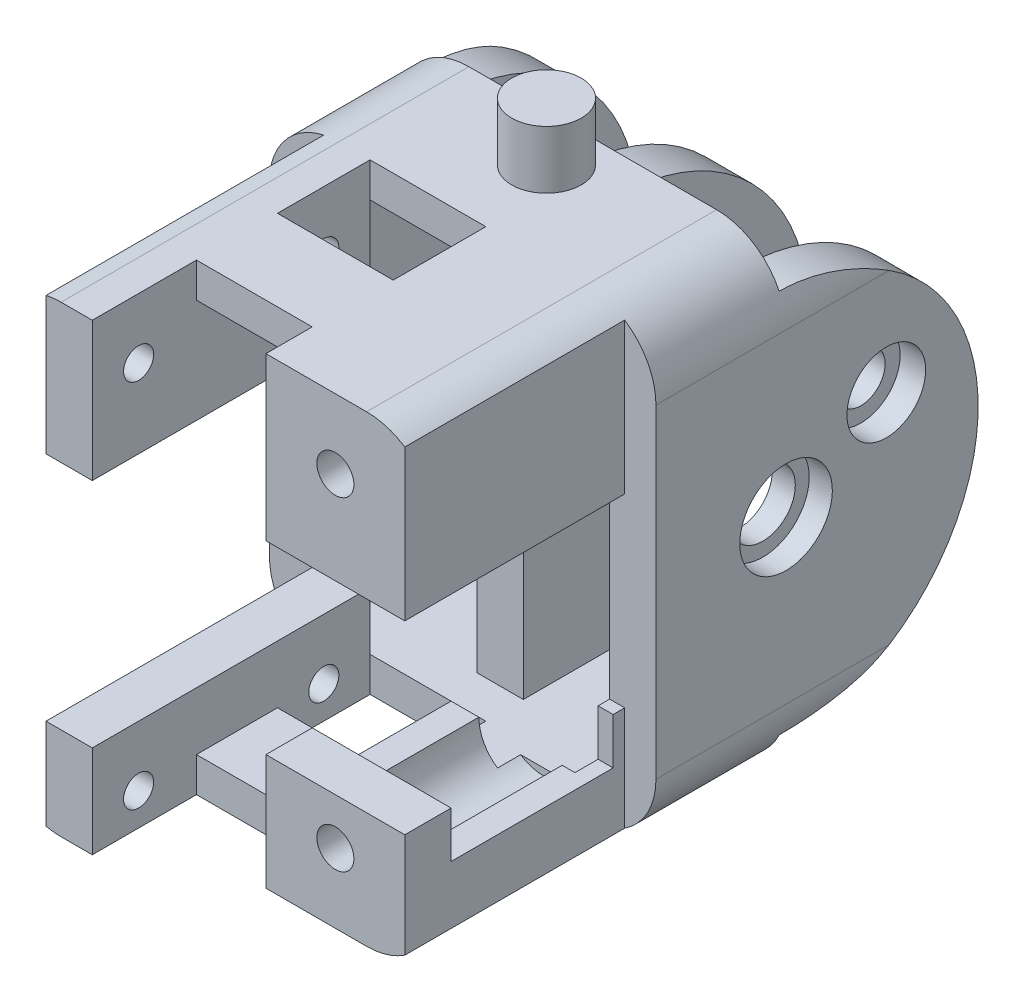
SolidWorks part; units mm, degrees
ref_plane "Front" through (0, 0, 0) normal (0, 0, 1) x (1, 0, 0)
ref_plane "Top" through (0, 0, 0) normal (0, 1, 0) x (1, 0, 0)
ref_plane "Right" through (0, 0, 0) normal (1, 0, 0) x (0, 0, -1)
sketch "Sketch1" plane through (0, 0, 0) normal (0, 0, 1) x (1, 0, 0)
  line L0 (8.35, -7) -> (8.35, 7)
  line L1 (-5.95, -8.5) -> (5.95, -8.5)
  line L2 (-6.35, -8.1) -> (-6.35, 8.1)
  line L3 (-5.95, 8.5) -> (5.95, 8.5)
  line L4 (6.35, -8.1) -> (6.35, 8.1)
  line L7 (-5.35, 10) -> (5.35, 10)
  line L8 (-8.35, -7) -> (-8.35, 7)
  line L9 (-5.35, -10) -> (5.35, -10)
  arc A8 (-5.95, 8.5) -> (-6.35, 8.1) centre (-5.95, 8.1) ccw
  arc A9 (6.35, 8.1) -> (5.95, 8.5) centre (5.95, 8.1) ccw
  arc A10 (5.95, -8.5) -> (6.35, -8.1) centre (5.95, -8.1) ccw
  arc A11 (-6.35, -8.1) -> (-5.95, -8.5) centre (-5.95, -8.1) ccw
  arc A13 (8.35, 7) -> (5.35, 10) centre (5.35, 7) ccw
  arc A14 (5.35, -10) -> (8.35, -7) centre (5.35, -7) ccw
  arc A15 (-8.35, -7) -> (-5.35, -10) centre (-5.35, -7) ccw
  arc A16 (-5.35, 10) -> (-8.35, 7) centre (-5.35, 7) ccw
  point P0 (0, 0)
  dimension "D1" = 3
  dimension "D6" = 3
  dimension "D9" = 3
  dimension "D2" = 0.4
  dimension "D3" = 0.4
  dimension "D5" = 0.4
  dimension "D7" = 0.4
  dimension "D8" = 3
  dimension "D4" = 16.7
extrude "Boss-Extrude1" add sketch "Sketch1" along normal blind 18 and the other way blind 12
sketch "Sketch9" plane through (0, 10, 0) normal (0, 1, 0) x (1, 0, 0)
  circle A0 centre (0, 0) radius 1.5
  dimension "D1" = 3
extrude "Boss-Extrude4" add sketch "Sketch9" along normal blind 2.5
sketch "Sketch10" plane through (0, -10, 0) normal (0, -1, 0) x (1, 0, 0)
  circle A0 centre (0, 0) radius 1.5
  dimension "D1" = 3
extrude "Boss-Extrude5" add sketch "Sketch10" along normal blind 2.5 contours A0
ref_plane "Plane1" through (0, 0, 3.5) normal (0, 0, 1) x (1, 0, 0)
sketch "Sketch16" plane through (0, 0, 3.5) normal (0, 0, 1) x (1, 0, 0)
  line L0 (8.35, -5.5) -> (8.35, 5.5)
  line L1 (-3.1, -8.5) -> (3.1, -8.5)
  line L2 (-6.1, -5.5) -> (-6.1, 5.5)
  line L3 (-3.1, 8.5) -> (4.3, 8.5)
  line L4 (6.1, -5.5) -> (6.1, 6.7)
  line L5 (-6.1, -8.5) -> (6.1, 8.5) construction
  line L6 (-6.1, 8.5) -> (6.1, -8.5) construction
  line L7 (-3.85, 10) -> (3.85, 10)
  line L8 (-8.35, -5.5) -> (-8.35, 5.5)
  line L9 (-3.85, -10) -> (3.85, -10)
  line L10 (0, 0) -> (0, -7)
  line L11 (0, -8.5) -> (0, -5.5)
  line L12 (0, -11.4125) -> (0, 11.4125) construction
  line L13 (0, -6) -> (-5, -6)
  line L14 (5, 0) -> (5, 6)
  line L15 (0, 0) -> (12.2753, 0) construction
  line L16 (0, 6) -> (5, 6)
  line L17 (0, 6) -> (-5, 6)
  line L18 (0, -6) -> (5, -6)
  line L19 (5, 0) -> (5, -6)
  line L20 (-5, 0) -> (-5, -6)
  line L21 (-5, 0) -> (-5, 6)
  line L22 (-6.058, 6) -> (-6.1, 6)
  arc A0 (3.1, -8.5) -> (6.1, -5.5) centre (3.1, -5.5) ccw
  arc A1 (-3.1, -8.5) -> (-6.1, -5.5) centre (-3.1, -5.5) cw
  arc A2 (4.3, 8.5) -> (6.1, 6.7) centre (4.3, 6.7) cw
  arc A3 (-6.1, 5.5) -> (-3.1, 8.5) centre (-3.1, 5.5) cw
  arc A4 (3.85, 10) -> (8.35, 5.5) centre (3.85, 5.5) cw
  arc A5 (-8.35, 5.5) -> (-3.85, 10) centre (-3.85, 5.5) cw
  arc A6 (-3.85, -10) -> (-8.35, -5.5) centre (-3.85, -5.5) cw
  arc A7 (3.85, -10) -> (8.35, -5.5) centre (3.85, -5.5) ccw
  circle A9 centre (0, 7) radius 0.6
  circle A11 centre (0, -7) radius 0.6
  circle A12 centre (0, 0) radius 5
  point P0 (-1.1, 0)
  dimension "D1" = 3
  dimension "D8" = 4.5
  dimension "D9" = 1.8
  dimension "D10" = 4.5
  dimension "D2" = 17
  dimension "D3" = 16.7
  dimension "D4" = 2.25
  dimension "D5" = 2.25
  dimension "D6" = 1.5
  dimension "D7" = 1.5
sketch "Sketch21" plane through (0, 0, 0) normal (1, 0, 0) x (0, 0, -1)
  line L0 (0, 0) -> (2, 0) construction
  line L1 (2, 0) -> (6.3301, 2.5) construction
  circle A0 centre (2, 0) radius 1.4
  circle A1 centre (6.3301, 2.5) radius 1.05
  circle A2 centre (2, 0) radius 5 construction
extrude "Extrude7" cut sketch "Sketch21" against normal through all both and the other way through all contours A0 L0 L1 | L0 A0 L1 region at (0, 0, -2)
sketch "Sketch23" plane through (0, 0, 0) normal (1, 0, 0) x (0, 0, -1)
  line L0 (2, 9.5) -> (2, 10)
  line L2 (2, -8.3) -> (2, -11.4416)
  line L4 (-9.4737, 11.5383) -> (19.1929, 11.5383)
  line L5 (-9.4737, 11.5383) -> (-9.4737, -11.4416)
  line L6 (2, 13.0446) -> (2, 10)
  line L7 (2, 4) -> (2, 9.5)
  line L8 (-9.4737, -11.4416) -> (19.1929, -11.4416)
  line L9 (2, -10.6179) -> (2, -4)
  line L10 (19.1929, 11.5383) -> (19.1929, -11.4416)
  circle A2 centre (2, 0) radius 4
  circle A4 centre (2, 0) radius 8.3
extrude "Extrude8" cut sketch "Sketch23" against normal through all both and the other way through all contours L2 L6 L0 region at (0, 0.0666, -12.5103)
sketch "Sketch25" plane through (0, 0, 0) normal (1, 0, 0) x (0, 0, -1)
  circle A0 centre (2, 0) radius 2
extrude "Extrude9" cut sketch "Sketch25" along normal blind 10 from offset 7.35 contours A0 region at (0, 0, -2)
mirror "Mirror1" about plane through (0, 0, 0) normal (1, 0, 0) of "Extrude9"
sketch "Sketch26" plane through (-7.35, 0, 0) normal (-1, 0, 0) x (0, 0, 1)
  line L13 (-2, 2.3671) -> (-4.05, 1.1836)
  line L14 (-4.05, 1.1836) -> (-4.05, -1.1836)
  line L15 (-4.05, -1.1836) -> (-2, -2.3671)
  line L16 (-2, -2.3671) -> (0.05, -1.1836)
  line L17 (0.05, -1.1836) -> (0.05, 1.1836)
  line L18 (0.05, 1.1836) -> (-2, 2.3671)
  circle A0 centre (-2, 0) radius 2.05 construction
extrude "Extrude10" cut sketch "Sketch26" along normal blind 10
sketch "Sketch27" plane through (0, 0, 0) normal (0, 1, 0) x (1, 0, 0)
  line L2 (-6.35, 10.3) -> (-6.35, 2.8)
  line L3 (0, 0) -> (0, 7.98)
  line L4 (6.35, 10.3) -> (6.35, 2.8)
  line L6 (-6.35, 10.3) -> (6.35, 10.3)
  line L7 (-5.55, 2) -> (0, 2)
  line L9 (0, 2) -> (5.55, 2)
  arc A6 (1.9843, 2.25) -> (-1.9843, 2.25) centre (0, 0) ccw
  arc A7 (-1.9843, 2.25) -> (-2.6458, 2) centre (-2.6458, 3) cw
  arc A8 (2.6458, 2) -> (1.9843, 2.25) centre (2.6458, 3) cw
  arc A9 (6.35, 2.8) -> (5.55, 2) centre (5.55, 2.8) cw
  arc A10 (-6.35, 2.8) -> (-5.55, 2) centre (-5.55, 2.8) ccw
  circle A11 centre (0, 0) radius 3
  dimension "D1" = 1
  dimension "D2" = 1
  dimension "D3" = 0.8
  dimension "D4" = 0.8
sketch "Sketch29" plane through (0, 0, 0) normal (0, 1, 0) x (1, 0, 0)
  circle A0 centre (0, 0) radius 3.5
extrude "Extrude12" add sketch "Sketch29" along normal blind 1.5 from offset 8.5
mirror "Mirror2" about plane through (0, 0, 0) normal (0, 1, 0) of "Extrude12"
extrude "Extrude13" cut sketch "Sketch27" against normal through all both and the other way through all contours L2 A10 L7 A7 A6 A8 L9 A9 L4 L6 | L9 A11 A6 L3 | A6 A11 L7 L3 | A11 A7 L7 | A11 L9 A8 region at (0, 0, -10.1483) region at (-2.2729, 0, -2.0529) region at (-0.8609, 0, -2.4063) region at (2.2729, 0, -2.0529) region at (0.8609, 0, -2.4063)
sketch "Sketch30" plane through (0, 0, 0) normal (1, 0, 0) x (0, 0, -1)
  line L0 (7, 0) -> (16.1032, 0) construction
  line L1 (0, 10) -> (-1.5, 10)
  line L2 (0, -8.5) -> (0, -14.6222)
  line L3 (-2, -10) -> (2, -10)
  line L5 (2, 8.3) -> (2, 10)
  line L6 (2, 10) -> (-1.5, 10)
  line L7 (2, -8.3) -> (2, -10)
  line L9 (0, 0) -> (-14, 0)
  line L11 (-2, -10) -> (0, -10)
  line L12 (0, 50) -> (0, -50) construction
  line L13 (-1.5, 10) -> (0, 10)
  line L14 (3, 8.5) -> (-9.1346, 8.5) construction
  line L15 (3, -8.5) -> (-1.0266, -8.5) construction
  line L16 (2, 0) -> (7, 0)
  line L18 (0, 0) -> (-2, 0)
  line L21 (-14, -10) -> (-14, 10)
  line L22 (2, 10) -> (-18, 10) construction
  line L23 (-14, 10) -> (-1.5, 10)
  line L24 (-14, -10) -> (-1.5, -10)
  line L25 (-2, 0) -> (-2, 13.6859)
  line L26 (-2, 0) -> (-2, -12.5408)
  arc A12 (2, -8.3) -> (2, 8.3) centre (2, 0) ccw
extrude "Extrude14" add sketch "Sketch30" along normal blind 1 and the other way blind 1 contours L11 | L3 | L13 | L1 | L11 | A12 | A12 region at (0, 9.7652, -1)
extrude "Extrude15" cut sketch "Sketch" along normal blind 10 and the other way blind 2 contours A1 region at (0, 2.5, -6.3301)
sketch "Sketch" plane through (0, 0, 0) normal (1, 0, 0) x (0, 0, -1) same geometry as "Sketch21"
sketch "Sketch32" plane through (0, 0, 0) normal (1, 0, 0) x (0, 0, -1)
  circle A0 centre (6.3301, 2.5) radius 1.7
extrude "Extrude17" cut sketch "Sketch32" along normal through all from offset 7.25
sketch "Sketch37" plane through (0, 0, 0) normal (1, 0, 0) x (0, 0, -1)
  circle A0 centre (2, 0) radius 1.35
extrude "Extrude22" cut sketch "Sketch37" against normal through all both and the other way through all
sketch "Sketch54" plane through (-1, 0, 0) normal (-1, 0, 0) x (0, 0, 1)
  line L1 (-5.5604, 4.3058) -> (-7.5091, 4.0695)
  line L2 (-7.5091, 4.0695) -> (-8.2788, 2.2637)
  line L3 (-8.2788, 2.2637) -> (-7.0999, 0.6942)
  line L4 (-7.0999, 0.6942) -> (-5.1512, 0.9305)
  line L5 (-5.1512, 0.9305) -> (-4.3814, 2.7363)
  line L6 (-4.3814, 2.7363) -> (-5.5604, 4.3058)
  circle A0 centre (-6.3301, 2.5) radius 1.7 construction
extrude "Extrude33" cut sketch "Sketch54" against normal blind 1.5
sketch "Sketch58" plane through (0, 0, 0) normal (1, 0, 0) x (0, 0, -1)
  line L0 (2, 0) -> (2, 17.3029) construction
  line L4 (-13.12, 0.097) -> (-13.12, -6.903)
  line L5 (-13.12, -6.903) -> (-5.58, -6.903)
  line L6 (-5.58, -6.903) -> (-5.58, 7.097)
  line L7 (-5.58, 7.097) -> (-13.12, 7.097)
  line L8 (-13.12, 7.097) -> (-13.12, 0.097)
  line L9 (-13.12, -6.903) -> (-13.12, -15.8392)
  line L10 (-13.12, -15.8392) -> (-23.547, -15.8392)
  line L11 (-23.547, -15.8392) -> (-23.547, 13.1188)
  line L12 (-23.547, 13.1188) -> (-13.12, 13.1188)
  line L13 (-13.12, 13.1188) -> (-13.12, 7.097)
  dimension "D1" = 15.12
extrude "Extrude36" cut sketch "Sketch58" along normal through all contours L13 L12 L11 L10 L9 L4 L8 region at (0, -1.3602, 18.3335)
sketch "Sketch60" plane through (0, 0, 13.12) normal (0, 0, 1) x (1, 0, 0)
  line L0 (0, 0) -> (4, 0)
  line L1 (50, 0) -> (-50, 0) construction
  line L2 (4, 0) -> (4, 7)
  line L3 (4, 0) -> (4, -7)
  line L5 (7, 3) -> (1, 3)
  line L6 (7, 3) -> (7, 11)
  line L7 (7, 11) -> (1, 11)
  line L8 (1, 3) -> (1, 11)
  line L9 (7, 3) -> (1, 11) construction
  line L10 (7, 11) -> (1, 3) construction
  line L15 (7, -9) -> (1, -9)
  line L16 (7, -9) -> (7, -5)
  line L17 (7, -5) -> (1, -5)
  line L18 (1, -9) -> (1, -5)
  line L19 (7, -9) -> (1, -5) construction
  line L20 (7, -5) -> (1, -9) construction
  circle A0 centre (4, 7) radius 0.8
  circle A1 centre (4, -7) radius 0.8
  arc M18 (6.35, -8.1) -> (5.95, -8.5) centre (5.95, -8.1) cw
  line M19 (5.95, -8.5) -> (0, -8.5)
  line M23 (0, 8.5) -> (5.95, 8.5)
  arc M24 (5.95, 8.5) -> (6.35, 8.1) centre (5.95, 8.1) cw
  line M25 (6.35, 8.1) -> (6.35, -8.1)
  dimension "D1" = 4
  dimension "D2" = 7
  dimension "D3" = 7
extrude "Extrude37" add sketch "Sketch60" against normal blind 8 contours A0 L5 L8 M25 M24 M23 | A1 L17 L18 M19 M18 M25 region at (3.6479, 5.6549, 13.12) region at (5.175, -5.0639, 13.12)
sketch "Sketch61" plane through (0, 0, 13.12) normal (0, 0, 1) x (1, 0, 0)
  line L0 (7, 11) -> (7, 12.9518)
  line L1 (7, 3) -> (1, 3)
  line L2 (7, 3) -> (7, 11)
  line L3 (7, 11) -> (1, 11)
  line L4 (1, 3) -> (1, 11)
  line L5 (7, 3) -> (1, 11) construction
  line L6 (7, 11) -> (1, 3) construction
  line L7 (7, -9) -> (1, -9)
  line L8 (7, -9) -> (7, -5)
  line L9 (7, -5) -> (1, -5)
  line L10 (1, -9) -> (1, -5)
  line L11 (7, -9) -> (1, -5) construction
  line L12 (7, -5) -> (1, -9) construction
  line L13 (7, 12.9518) -> (12.7978, 12.9518)
  line L14 (12.7978, 12.9518) -> (12.7978, -12.6418)
  line L15 (12.7978, -12.6418) -> (7, -12.6418)
  line L16 (7, -12.6418) -> (7, -9)
  line L17 (1, -5) -> (1, 3)
  line L18 (1, 11) -> (1, 15.1958)
  line L19 (1, 15.1958) -> (-6, 15.1958)
  line L20 (-6, 15.1958) -> (-6, -14.1587)
  line L21 (-6, -14.1587) -> (1, -14.1587)
  line L22 (1, -14.1587) -> (1, -9)
  line L23 (-6, 0.5185) -> (-4, 0.5185)
  line L24 (-6, -14.1587) -> (-20.1077, -14.1587)
  line L25 (-6, -14.1587) -> (-6, 15.1958)
  line L26 (-6, 15.1958) -> (-20.1077, 15.1958)
  line L27 (-20.1077, -14.1587) -> (-20.1077, 15.1958)
  line L28 (-4, 0.5185) -> (-4, -18.5267)
  line L29 (-4, 0.5185) -> (-4, 18.7046)
  point P0 (4, 7)
  point P6 (4, -7)
  line M9 (6.35, 3) -> (6.35, -5)
  line M10 (6.35, -5) -> (1, -5)
  line M11 (1, -5) -> (1, -8.5)
  line M12 (1, -8.5) -> (0, -8.5)
  line M16 (0, 8.5) -> (1, 8.5)
  line M17 (1, 8.5) -> (1, 3)
  line M18 (1, 3) -> (6.35, 3)
  line M22 (0, -10) -> (5.35, -10)
  arc M23 (5.35, -10) -> (8.35, -7) centre (5.35, -7) ccw
  line M24 (8.35, -7) -> (8.35, 7)
  arc M25 (8.35, 7) -> (5.35, 10) centre (5.35, 7) ccw
  line M26 (5.35, 10) -> (0, 10)
  line M51 (0, -8.5) -> (0, -10)
  line M52 (0, 10) -> (0, 8.5)
  dimension "D1" = 8
  dimension "D2" = 6
  dimension "D3" = 4
  dimension "D4" = 6
  dimension "D5" = 7
extrude "Extrude38" cut sketch "Sketch61" against normal blind 9.5 and the other way through all contours L17 M10 M9 M18 | L16 L2 L1 L9 L8 M23 M24 M25 M9 | L16 L15 L14 L13 L0 L2 M25 M24 M23 | L27 L24 L20 L26 region at (10.3255, 0.1844, 13.12) region at (7.4745, -0.1802, 13.12) region at (3.675, -1, 13.12) region at (-13.0538, 0.5185, 13.12)
sketch "Sketch62" plane through (0, 0, 13.12) normal (0, 0, 1) x (1, 0, 0)
  line L0 (2.2, 7) -> (2.2, 1.6106)
  line L1 (2.2, 1.6106) -> (5.8, 1.6106)
  line L2 (5.8, 1.6106) -> (5.8, 7)
  line L3 (2.2, -7) -> (-2.919, -7)
  line L4 (-2.919, -7) -> (-2.919, -3.3756)
  line L5 (-2.919, -3.3756) -> (10.7091, -3.3756)
  line L6 (5.8, -7) -> (10.7091, -7)
  line L7 (10.7091, -7) -> (10.7091, -3.3756)
  circle A0 centre (4, 7) radius 1.8
  circle A1 centre (4, -7) radius 1.8
  circle M1 centre (4, 7) radius 0.8
  line M4 (1, 3) -> (7, 3)
extrude "Extrude39" cut sketch "Sketch62" against normal blind 7 from offset 2 contours A0 L0 L2 M4 | L1 L2 L0 M4 | A0 M1 region at (4, 4.3243, 13.12) region at (4, 8.7491, 13.12) region at (4, 2.3053, 13.12) offset against normal yes
extrude "Extrude40" cut sketch "Sketch" against normal blind 7 from offset 2 contours A1 | A1 L6 L7 L5 L4 L3 region at (3.883, -5.0674, 13.12) region at (4, -7, 13.12) offset against normal yes
sketch "Sketch" plane through (0, 0, 13.12) normal (0, 0, 1) x (1, 0, 0) same geometry as "Sketch62"
sketch "Эскиз1" plane through (-6, 0, 0) normal (1, 0, 0) x (0, 0, -1)
  line L0 (0, 0) -> (-13.12, 0)
  line L1 (50, 0) -> (-50, 0) construction
  line L2 (-13.12, 0) -> (-13.12, -7) construction
  line L3 (-13.12, -7) -> (-15.1769, -7) construction
  line L4 (-13.12, 0) -> (-13.12, 7) construction
  line L5 (-13.12, 7) -> (-18.3274, 7) construction
  line L7 (-16.2677, -3) -> (-10.6385, -3) construction
  line L9 (-9.62, -1.3283) -> (-9.62, -4.7407) construction
  circle A1 centre (-9.62, -3) radius 5
  circle A2 centre (2, 0) radius 8
  circle A3 centre (2, 0) radius 10
  circle A4 centre (-9.62, -3) radius 7
  point P7 (-9.62, -3)
  dimension "D1" = 7
  dimension "D2" = 7
  dimension "D3" = 3
  dimension "D4" = 3.5
sketch "Эскиз5" plane through (0, 0, 0) normal (1, 0, 0) x (0, 0, -1)
  line L0 (2, 0) -> (-13.12, 0)
  line L1 (-13.12, 0) -> (-13.12, 1)
  line L2 (-13.12, 1) -> (-9.62, 1)
  line L3 (-9.62, 1) -> (-9.62, 2)
  line L4 (-9.62, 2) -> (-15.62, 2)
  line L6 (-15.62, 2) -> (-24.0391, 2)
  line L7 (-15.62, 2) -> (-15.62, 12.4543)
  line L8 (-15.62, 12.4543) -> (-24.0391, 12.4543)
  line L9 (-24.0391, 2) -> (-24.0391, 12.4543)
  line L10 (-15.62, 2) -> (-24.0391, 2)
  line L11 (-15.62, 2) -> (-15.62, -11.4449)
  line L12 (-15.62, -11.4449) -> (-24.0391, -11.4449)
  line L13 (-24.0391, 2) -> (-24.0391, -11.4449)
extrude "Вырез-Вытянуть2" cut sketch "Эскиз5" against normal through all both and the other way through all contours L9 L6 L7 L8 | L6 L13 L12 L11 region at (0, -4.7225, 19.8296) region at (0, 7.2271, 19.8296)
sketch "Эскиз3" plane through (-6, 0, 0) normal (-1, 0, 0) x (0, 0, 1)
  line L0 (-2, 0) -> (15.62, 0)
  line L6 (15.62, -9) -> (15.62, 9)
  line L7 (15.62, 9) -> (3.62, 9)
  line L8 (3.62, 9) -> (3.62, -9)
  line L9 (15.62, -9) -> (3.62, -9)
  point P7 (3.62, 0)
  line M3 (3.62, 8.4969) -> (15.62, 8.4969)
extrude "Бобышка-Вытянуть2" add sketch "Эскиз3" against normal blind 2 contours M3 | L7 M3 | L9 L6 L0 L8 region at (-6, 4.2484, 9.62) region at (-6, -4.5, 9.62) region at (-6, 8.7484, 9.62)
sketch "Эскиз4" plane through (-6, 0, 0) normal (-1, 0, 0) x (0, 0, 1)
  line L0 (15.62, 0) -> (-2, 0)
  line L2 (15.62, 0) -> (15.62, -6)
  line L3 (15.62, -6) -> (3.62, -6)
  line L5 (3.62, -6) -> (3.62, 0)
  line L6 (15.62, 0) -> (15.62, 4)
  line L7 (15.62, 4) -> (3.62, 4)
  line L9 (3.62, 4) -> (3.62, 0)
  dimension "D1" = 17.62
extrude "Вырез-Вытянуть1" cut sketch "Эскиз4" against normal blind 2 contours L7 | L3 region at (-6, -3, 9.62) region at (-6, 2, 9.62)
sketch "Эскиз6" plane through (-6, 0, 0) normal (-1, 0, 0) x (0, 0, 1)
  line L0 (-2, 0) -> (13.12, 0)
  line L1 (13.12, 0) -> (13.12, -3)
  line L2 (13.12, -3) -> (9.62, -3)
  line L3 (9.62, -3) -> (5.62, -3)
  line L4 (5.62, -3) -> (5.62, -8.6)
  line L5 (9.62, -3) -> (9.62, 12.5394) construction
  line L6 (5.62, -3) -> (5.62, 7.4)
  line L7 (13.62, -3) -> (13.62, 7.4)
  line L8 (13.62, -3) -> (13.62, -8.6)
  circle A0 centre (9.62, -3) radius 1
  circle A1 centre (5.62, 7.4) radius 0.65
  circle A2 centre (5.62, -8.6) radius 0.65
  circle A3 centre (13.62, -8.6) radius 0.65
  circle A4 centre (13.62, 7.4) radius 0.65
  dimension "D1" = 4
  dimension "D2" = 3.5
  dimension "D3" = 4
extrude "Вырез-Вытянуть3" cut sketch "Эскиз6" against normal blind 2 contours A1 | A4 | A2 | A3 region at (-6, -8.1534, 6.0666) region at (-6, 7.8466, 5.1734) region at (-6, 7.8466, 13.1734) region at (-6, -8.1534, 14.0666)
extrude "Вырез-Вытянуть4" cut sketch "Sketch61<3>" along normal through all and the other way blind 2 contours L29 L28 L21 L22 L17 L4 L18 L19 M22 M51 M12 M11 M17 M16 M52 M26 | L4 M16 M26 M52 | L22 L10 M22 M12 M51 region at (-1.5417, 0.5293, 13.12) region at (0.5, 9.25, 13.12) region at (0.5, -9.25, 13.12)
sketch "Sketch61<3>" plane through (0, 0, 13.12) normal (0, 0, 1) x (1, 0, 0) same geometry as "Sketch61"
extrude "Вырез-Вытянуть5" cut sketch "Sketch61<4>" against normal blind 4 from offset 5.5 contours L29 L28 L21 L22 L17 L4 L18 L19 M22 M51 M12 M11 M17 M16 M52 M26 | L4 M16 M26 M52 | L22 L10 M22 M12 M51 region at (-1.5417, 0.5293, 13.12) region at (0.5, 9.25, 13.12) region at (0.5, -9.25, 13.12) offset against normal yes
sketch "Sketch61<4>" plane through (0, 0, 13.12) normal (0, 0, 1) x (1, 0, 0) same geometry as "Sketch61"
